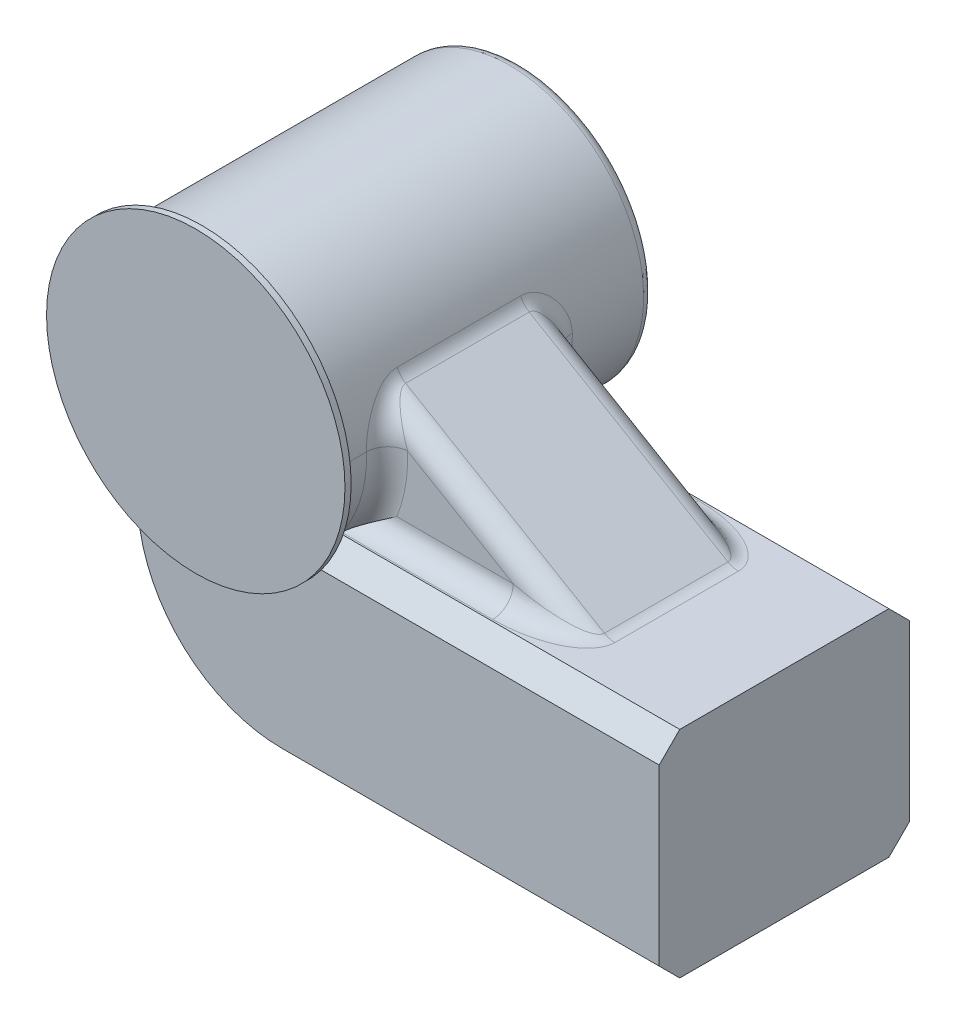
SolidWorks part; units mm, degrees
ref_plane "Piano frontale" through (0, 0, 0) normal (0, 0, 1) x (1, 0, 0)
ref_plane "Piano superiore" through (0, 0, 0) normal (0, 1, 0) x (1, 0, 0)
ref_plane "Piano destro" through (0, 0, 0) normal (1, 0, 0) x (0, 0, -1)
ref_plane "PianoEstrusione" through (0, 0, 68) normal (0, 0, -1) x (-1, 0, 0)
sketch "Schizzo1" plane through (0, 0, 68) normal (0, 0, -1) x (-1, 0, 0)
  circle A0 centre (0, 0) radius 72.5
  dimension "D1" = 145
extrude "CorpoContatto" add sketch "Schizzo1" along normal blind 3
sketch "Schizzo2" plane through (0, 0, 65) normal (0, 0, -1) x (-1, 0, 0)
  circle A0 centre (0, 0) radius 65
  dimension "D1" = 130
extrude "Corpo" add sketch "Schizzo2" along normal blind 154.63
ref_plane "PianoCorpoRettangolare" through (89, 0, 0) normal (1, 0, 0) x (0, 0, -1)
sketch "Schizzo3" plane through (89, 0, 0) normal (1, 0, 0) x (0, 0, -1)
  line L0 (0, 0) -> (0, -90) construction
  line L2 (60.805, -37.695) -> (-60.805, -37.695)
  line L3 (60.805, -37.695) -> (60.805, -142.305)
  line L4 (60.805, -142.305) -> (-60.805, -142.305)
  line L5 (-60.805, -37.695) -> (-60.805, -142.305)
  line L6 (60.805, -37.695) -> (-60.805, -142.305) construction
  line L7 (60.805, -142.305) -> (-60.805, -37.695) construction
  dimension "D1" = 90
  dimension "D2" = 104.61
  dimension "D3" = 121.61
extrude "CorpoRettangolare" add sketch "Schizzo3" along normal blind 128.98 separate body
sketch "Schizzo4" plane through (0, 0, 0) normal (0, 0, 1) x (1, 0, 0)
  line L0 (89, -142.305) -> (89, -37.695) construction
  line L1 (89, -142.305) -> (89, -37.695)
  line L2 (-45.4, -46.5171) -> (-45.4, -62.305)
  line L3 (34.6, -142.305) -> (89, -142.305)
  line L4 (89, -37.695) -> (52.9536, -37.695)
  circle A0 centre (0, 0) radius 65 construction
  arc A1 (-45.4, -46.5171) -> (52.9536, -37.695) centre (0, 0) ccw
  arc A2 (-45.4, -62.305) -> (34.6, -142.305) centre (34.6, -62.305) ccw
  point P10 (-45.4, -142.305)
  dimension "D2" = 80
  dimension "D1" = 134.4
extrude "CorpoDaRaccordare" add sketch "Schizzo4" along normal mid plane 121.61
chamfer "Smusso" distance 10 angle 45 8 edges at (-45.4, -54.411, 60.805) (-21.9685, -118.8735, 60.805) (126.29, -142.305, 60.805) (135.4668, -37.695, 60.805) (135.4668, -37.695, -60.805) (-45.4, -54.411, -60.805) (-21.9685, -118.8735, -60.805) (126.29, -142.305, -60.805)
sketch "Schizzo5" plane through (0, 0, 0) normal (0, 0, 1) x (1, 0, 0)
  line L0 (217.98, -37.695) -> (52.9536, -37.695) construction
  line L1 (162.9536, -37.695) -> (52.9536, -37.695)
  line L2 (162.9536, -37.695) -> (61.0531, 22.305)
  circle A0 centre (0, 0) radius 65 construction
  arc A1 (52.9536, -37.695) -> (61.0531, 22.305) centre (0, 0) ccw
  dimension "D1" = 110
  dimension "D2" = 60
extrude "Nervatura" add sketch "Schizzo5" along normal mid plane 80
fillet "RaccordoNervatura" radius 10 8 edges at (107.9536, -37.695, 40) (64.4157, -8.6956, 40) (162.9536, -37.695, 0) (61.0531, 22.305, 0) (107.9536, -37.695, -40) (112.0034, -7.695, -40) (64.4157, -8.6956, -40) (112.0034, -7.695, 40)
fillet "RaccordoLaterale" radius 5 2 edges at (-65, 0, 65) (-65, 0, -89.63)
sketch "SchizzoAccoppiamentoGiunto4" plane through (217.98, 0, 0) normal (1, 0, 0) x (0, 0, -1)
  line L0 (-60.805, -47.695) -> (-60.805, -132.305) construction
  line L1 (-50.805, -142.305) -> (50.805, -142.305) construction
  circle A0 centre (0, -90) radius 52.305
  point P5 (-60.805, -90)
  point P9 (0, -142.305)
